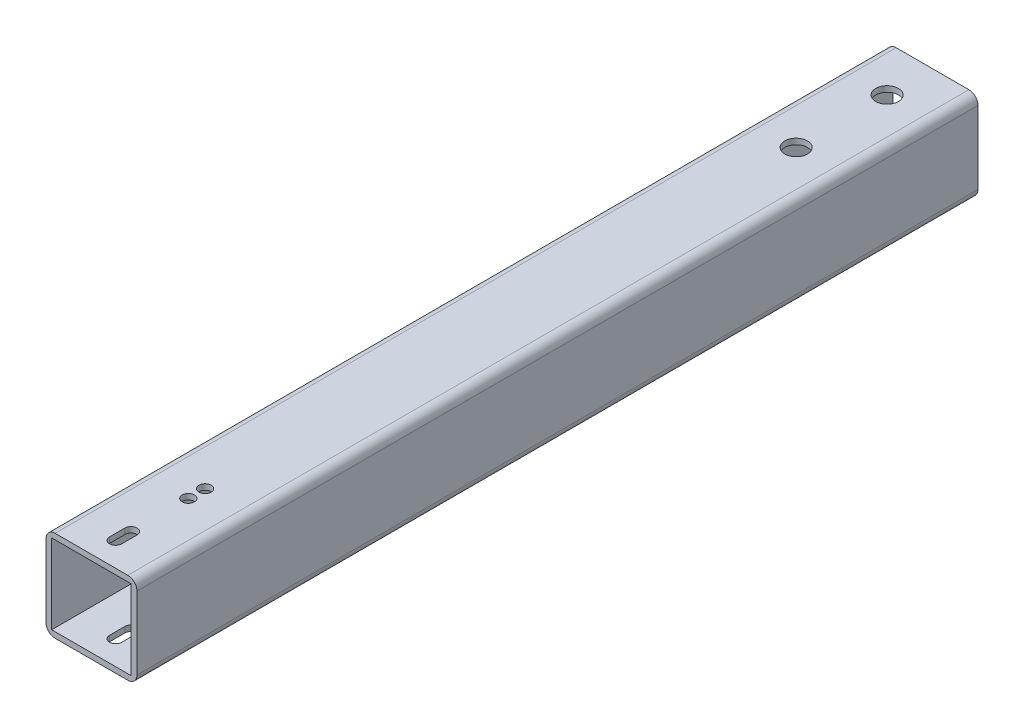
SolidWorks part; units mm, degrees
ref_plane "Front Plane" through (0, 0, 0) normal (0, 0, 1) x (1, 0, 0)
ref_plane "Top Plane" through (0, 0, 0) normal (0, 1, 0) x (1, 0, 0)
ref_plane "Right Plane" through (0, 0, 0) normal (1, 0, 0) x (0, 0, -1)
sketch "Sketch1" plane through (0, 0, 0) normal (0, 0, 1) x (1, 0, 0)
  line L1 (-24.2596, 11.4248) -> (1.1404, 11.4248)
  line L2 (-24.2596, 11.4248) -> (-24.2596, -13.9752)
  line L3 (-24.2596, -13.9752) -> (1.1404, -13.9752)
  line L4 (1.1404, 11.4248) -> (1.1404, -13.9752)
  line L5 (-22.6721, 9.8373) -> (-0.4471, 9.8373)
  line L6 (-22.6721, 9.8373) -> (-22.6721, -12.3877)
  line L7 (-22.6721, -12.3877) -> (-0.4471, -12.3877)
  line L8 (-0.4471, 9.8373) -> (-0.4471, -12.3877)
  dimension "D1" = 25.4
  dimension "D2" = 25.4
  dimension "D3" = 1.5875
  dimension "D4" = 1.5875
  dimension "D5" = 1.5875
  dimension "D6" = 1.5875
extrude "Boss-Extrude1" add sketch "Sketch1" along normal blind 234.95
fillet "Fillet1" radius 2.54 4 edges at (1.1404, -13.9752, 117.475) (-24.2596, -13.9752, 117.475) (-24.2596, 11.4248, 117.475) (1.1404, 11.4248, 117.475)
sketch "Sketch2" plane through (0, 11.4248, 0) normal (0, 1, 0) x (1, 0, 0)
  line L0 (-1.3996, 0) -> (-21.7196, 0) construction
  line L1 (0, 0) -> (0, -59.7417) construction
  line L2 (-11.5596, -12.7) -> (-11.5596, 0) construction
  line L3 (-1.3996, -234.95) -> (-1.3996, 0) construction
  line L4 (-21.7196, -50.8) -> (29.3119, -50.8) construction
  line L5 (-21.7196, 0) -> (-21.7196, -234.95) construction
  circle A0 centre (-11.5596, -12.7) radius 3.175
  circle A2 centre (-11.5596, -38.1) radius 3.175
  dimension "D1" = 6.35
  dimension "D2" = 12.7
  dimension "D3" = 6.35
  dimension "D4" = 50.8
  dimension "D6" = 25.4
extrude "Cut-Extrude1" cut sketch "Sketch2" against normal through all
sketch "Sketch3" plane through (0, 11.4248, 0) normal (0, 1, 0) x (1, 0, 0)
  line L0 (-11.5596, -215.9) -> (-15.3182, -190.7796) construction
  line L1 (-11.5596, -215.9) -> (13.426, -212.1616) construction
  line L2 (-11.5596, -215.9) -> (-29.2422, -202.8202) construction
  line L3 (-11.5596, -215.9) -> (-11.5596, -196.7728) construction
  line L4 (-11.5596, -12.7) -> (-11.5596, -270.3313) construction
  line L5 (-11.5596, -223.9) -> (-11.5596, -228.195) construction
  line L6 (-9.8596, -223.9) -> (-9.8596, -228.195)
  line L7 (-13.2596, -223.9) -> (-13.2596, -228.195)
  line L11 (-11.5596, -215.9) -> (30.1254, -215.9) construction
  line L12 (-37.8321, -50.8) -> (104.3326, -50.8) construction
  line L13 (-1.3996, 0) -> (-21.7196, 0) construction
  circle A0 centre (-11.5596, -207.9) radius 1.7
  circle A1 centre (-11.5596, -203.195) radius 1.7
  circle A2 centre (-11.5596, -215.9) radius 20.9 construction
  arc A6 (-9.8596, -223.9) -> (-13.2596, -223.9) centre (-11.5596, -223.9) ccw
  arc A7 (-13.2596, -228.195) -> (-9.8596, -228.195) centre (-11.5596, -228.195) ccw
  point P12 (-11.5596, -223.9)
  point P14 (0, 0)
  point P15 (-9.8596, -223.9)
  point P16 (0, 0)
  point P17 (-11.5596, -196.9907)
  point P21 (-11.5596, -226.0475)
  point P27 (-11.5596, -226.0475)
  point P33 (-11.5596, 0)
  point P38 (0, 0)
  point P39 (0, 0)
  point P40 (0, 0)
  point P41 (0, 0)
  point P42 (-11.5596, -228.195)
  point P43 (0, 0)
  dimension "D1" = 215.9
  dimension "D2" = 3.4
  dimension "D3" = 3.4
  dimension "D13" = 41.8
  dimension "D6" = 3.4
  dimension "D7" = 16
  dimension "D8" = 25
  dimension "D10" = 8
  dimension "D14" = 50.8
extrude "Cut-Extrude2" cut sketch "Sketch3" against normal through all and the other way through all
